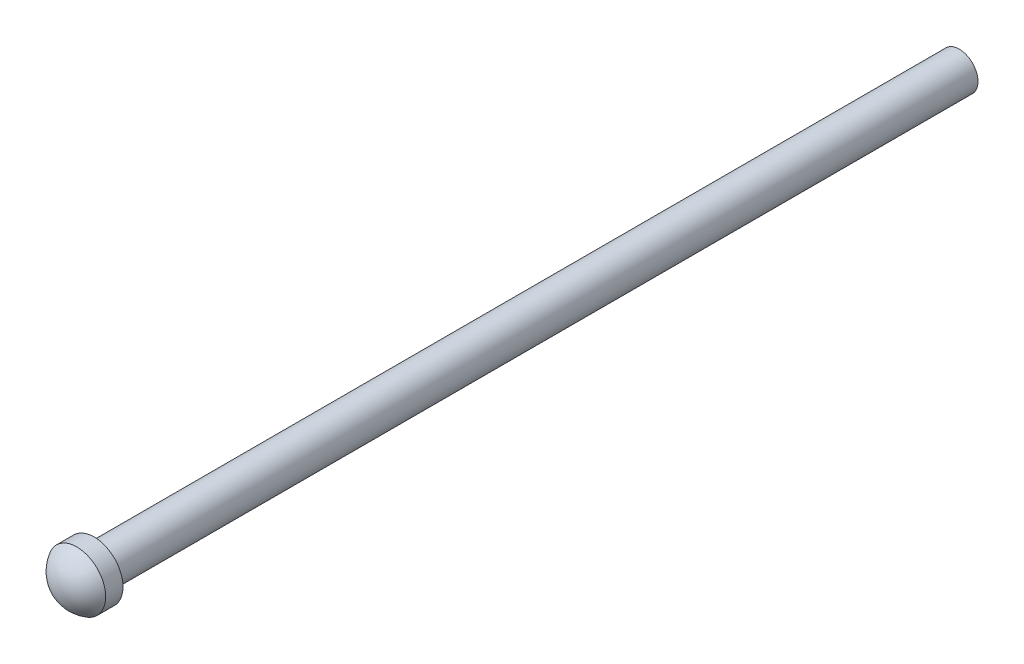
SolidWorks part; units mm, degrees
ref_plane "Front Plane" through (0, 0, 0) normal (0, 0, 1) x (1, 0, 0)
ref_plane "Top Plane" through (0, 0, 0) normal (0, 1, 0) x (1, 0, 0)
ref_plane "Right Plane" through (0, 0, 0) normal (1, 0, 0) x (0, 0, -1)
sketch "Sketch1" plane through (0, 0, 0) normal (0, 0, 1) x (1, 0, 0)
  circle A2 centre (5, 60) radius 3.25
  circle A3 centre (5, 60) radius 3.25
  dimension "D1" = 0.25
sketch "Sketch2" plane through (0, 0, 0) normal (1, 0, 0) x (0, 0, -1)
  line L0 (0, 0) -> (150, 0) construction
  line L1 (0, 0) -> (150, 0)
sweep "Sweep1" add profiles "Sketch1" path "Sketch2"
sketch "Sketch3" plane through (0, 0, 0) normal (0, 0, 1) x (1, 0, 0)
  circle A0 centre (5, 60) radius 5
  arc A2 (10, 60) -> (0, 60) centre (5, 60) ccw construction
extrude "Boss-Extrude1" add sketch "Sketch3" along normal blind 3
dome "Dome1" faces to dome 1 distance 3 reverse direction no elliptical dome no face at (10, 60, 3) parameters "D1"=3
